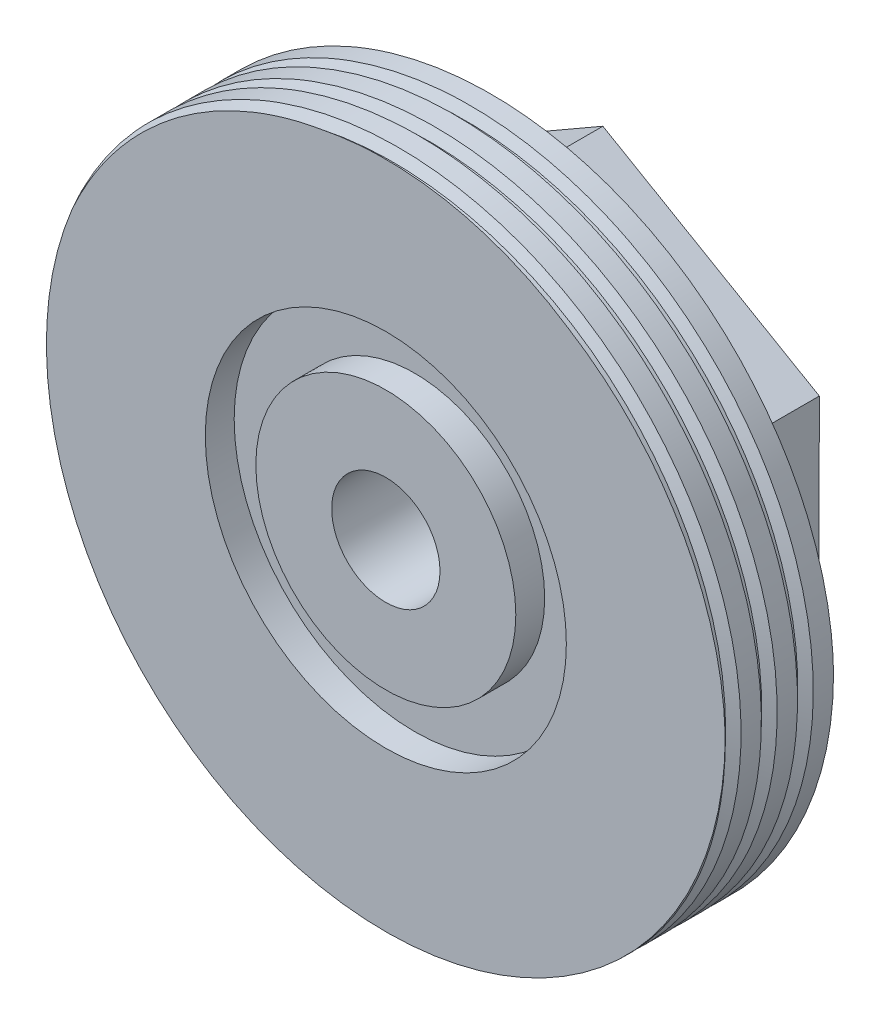
SolidWorks part; units mm, degrees
ref_plane "Front Plane" through (0, 0, 0) normal (0, 0, 1) x (1, 0, 0)
ref_plane "Top Plane" through (0, 0, 0) normal (0, 1, 0) x (1, 0, 0)
ref_plane "Right Plane" through (0, 0, 0) normal (1, 0, 0) x (0, 0, -1)
sketch "Sketch3" plane through (0, 0, 0) normal (0, 0, 1) x (1, 0, 0)
  circle A3 centre (8.3476, 27.7238) radius 14.9225
  dimension "D1" = 29.845
extrude "Boss-Extrude1" add sketch "Sketch3" against normal blind 9.525 contours A3 region at (8.3476, 27.7238, 0)
sketch "Sketch11" plane through (0, 0, 0) normal (0, 0, 1) x (1, 0, 0)
  circle A0 centre (8.3476, 27.7238) radius 2.3813
  dimension "D1" = 4.7625
extrude "Cut-Extrude3" cut sketch "Sketch11" against normal blind 6.35
sketch "Sketch12" plane through (0, 0, 0) normal (0, 0, 1) x (1, 0, 0)
  circle A0 centre (8.3476, 27.7238) radius 5.715
  circle A1 centre (8.3476, 27.7238) radius 7.9375
  dimension "D1" = 15.875
  dimension "D2" = 11.43
extrude "Cut-Extrude4" cut sketch "Sketch12" against normal blind 1.27
thread "Thread1" pitch 0.7937 method cut profile "Thread Profile1" start angle 0, offset 0.7937, length 7.62, pitch 1.5875, diameter 29.845
ref_plane "Plane1" through (-6.5749, 27.7238, 0.7937) normal (0, -1, 0) x (-1, 0, 0)
sketch "Thread Profile1" plane through (-6.5749, 27.7238, 0.7937) normal (0, -1, 0) x (-1, 0, 0)
  line L0 (0, 0) -> (0, 0.7937) construction
  line L11 (0, 0) -> (0, 0.6945)
  line L12 (0, 0.6945) -> (-0.4296, 0.4465)
  line L13 (-0.4296, 0.4465) -> (-0.4296, 0.248)
  line L15 (-0.4296, 0.248) -> (0, 0)
  line L17 (-0.4296, 0.3473) -> (0, 0.3473) construction
  point P2 (0, 0)
  dimension "Pitch" = 0.7937
  dimension "Profile_Angle" = 60
  dimension "Profile_Land" = 0.1984
  dimension "Profile_Height" = 0.4296
sketch "Sketch13" plane through (0, 0, -9.525) normal (0, 0, -1) x (-1, 0, 0)
  circle A0 centre (-8.3476, 27.7238) radius 2.3813
extrude "Cut-Extrude5" cut sketch "Sketch13" against normal blind 6.35
sketch "Sketch14" plane through (0, 0, -9.525) normal (0, 0, -1) x (-1, 0, 0)
  line L1 (1.1867, 22.2406) -> (1.1681, 33.2391)
  line L2 (1.1681, 33.2391) -> (-8.3661, 38.7223)
  line L3 (-8.3661, 38.7223) -> (-17.8818, 33.207)
  line L4 (-17.8818, 33.207) -> (-17.8633, 22.2085)
  line L5 (-17.8633, 22.2085) -> (-8.3291, 16.7253)
  line L6 (-8.3291, 16.7253) -> (1.1867, 22.2406)
  circle A0 centre (-8.3476, 27.7238) radius 9.525 construction
  circle A3 centre (-8.3476, 27.7238) radius 14.9225
  circle A4 centre (-8.3476, 27.7238) radius 14.9225
  dimension "D2" = 0
  dimension "D1" = 19.05
extrude "Cut-Extrude6" cut sketch "Sketch14" against normal blind 4.7625
ref_point "Point1"
